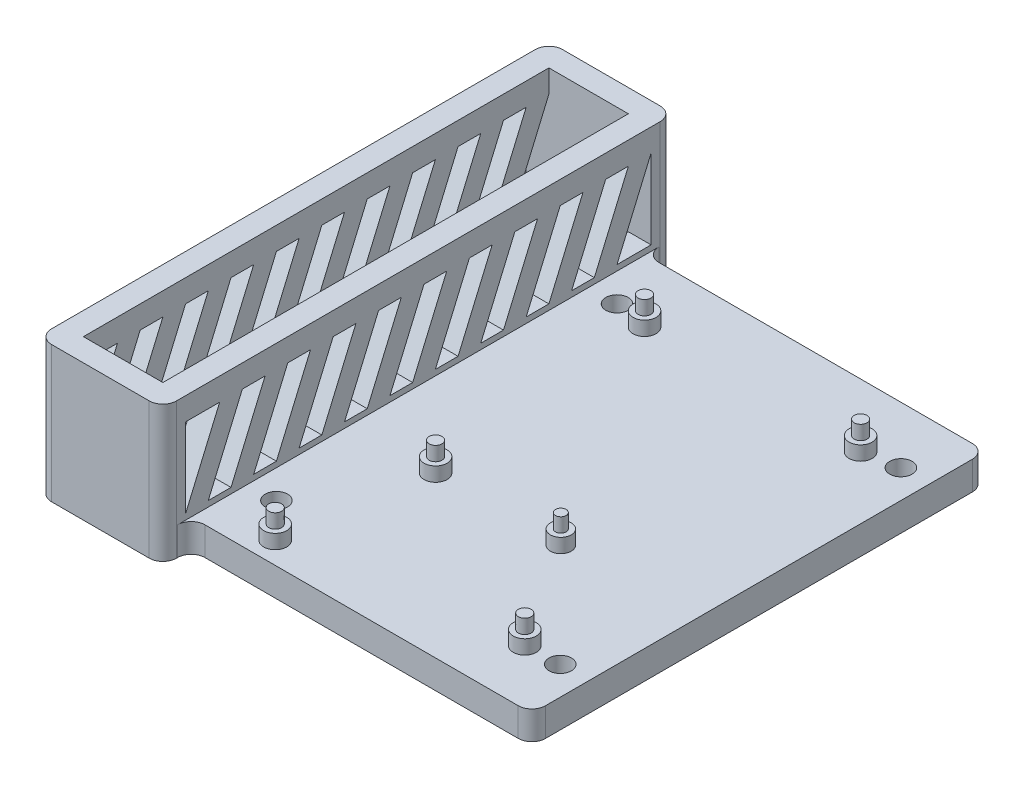
SolidWorks part; units mm, degrees
ref_plane "Front Plane" through (0, 0, 0) normal (0, 0, 1) x (1, 0, 0)
ref_plane "Top Plane" through (0, 0, 0) normal (0, 1, 0) x (1, 0, 0)
ref_plane "Right Plane" through (0, 0, 0) normal (1, 0, 0) x (0, 0, -1)
sketch "Sketch1" plane through (0, 0, 0) normal (0, 1, 0) x (1, 0, 0)
  line L1 (-38.1, -50.8) -> (38.1, -50.8)
  line L2 (-38.1, -50.8) -> (-38.1, 50.8)
  line L3 (-38.1, 50.8) -> (38.1, 50.8)
  line L4 (38.1, -50.8) -> (38.1, 50.8)
  line L5 (-38.1, -50.8) -> (38.1, 50.8) construction
  line L6 (-38.1, 50.8) -> (38.1, -50.8) construction
  circle A0 centre (-31.75, 38.1) radius 2.5
  circle A1 centre (-31.75, -38.1) radius 2.5
  circle A2 centre (31.75, 38.1) radius 2.5
  circle A3 centre (31.75, -38.1) radius 2.5
  point P0 (0, 0)
  dimension "D3" = 5
  dimension "D1" = 76.2
  dimension "D2" = 101.6
  dimension "D4" = 6.35
  dimension "D5" = 6.35
  dimension "D6" = 12.7
  dimension "D7" = 12.7
extrude "Boss-Extrude1" add sketch "Sketch1" along normal blind 6.35
sketch "Sketch2" plane through (0, 6.35, 0) normal (0, 1, 0) x (1, 0, 0)
  circle A0 centre (-24.1681, -45.9486) radius 1.5621 construction
  circle A1 centre (24.1681, -38.4556) radius 1.5621 construction
  circle A2 centre (-19.2896, -14.9479) radius 1.5621 construction
  circle A3 centre (8.7266, -14.9479) radius 1.3153 construction
  circle A4 centre (-24.1681, 36.6776) radius 1.5621 construction
  circle A5 centre (24.1681, 36.6776) radius 1.5621 construction
  circle A6 centre (-24.1681, -45.9486) radius 1.5621 construction
  circle A7 centre (24.1681, -38.4556) radius 1.5621 construction
  circle A8 centre (-19.2896, -14.9479) radius 1.5621 construction
  circle A9 centre (8.7266, -14.9479) radius 1.3153 construction
  circle A10 centre (-24.1681, 36.6776) radius 1.5621 construction
  circle A11 centre (24.1681, 36.6776) radius 1.5621 construction
  circle A12 centre (-24.1681, 36.6776) radius 2.5781
  circle A13 centre (24.1681, 36.6776) radius 2.5781
  circle A14 centre (-19.2896, -14.9479) radius 2.5781
  circle A15 centre (24.1681, -38.4556) radius 2.5781
  circle A16 centre (-24.1681, -45.9486) radius 2.5781
  circle A17 centre (-24.1681, 36.6776) radius 1.4351
  circle A18 centre (24.1681, 36.6776) radius 1.4351
  circle A19 centre (-19.2896, -14.9479) radius 1.4351
  circle A20 centre (-24.1681, -45.9486) radius 1.4351
  circle A21 centre (24.1681, -38.4556) radius 1.4351
  circle A22 centre (8.7266, -14.9479) radius 1.1883
  circle A23 centre (8.7266, -14.9479) radius 2.3313
  dimension "D1" = 1.016
  dimension "D2" = 0.127
  dimension "D3" = 0.127
  dimension "D4" = 1.016
extrude "Boss-Extrude2" add sketch "Sketch2" along normal blind 3.175 contours A17 | A12 A17 | A18 | A13 A18 | A19 | A14 A19 | A22 | A23 A22 | A20 | A16 A20 | A21 | A15 A21 region at (-26.6733, 6.35, -36.6776) region at (21.6629, 6.35, -36.6776) region at (-21.7948, 6.35, 14.9479) region at (21.6629, 6.35, 38.4556) region at (-26.6733, 6.35, 45.9486) region at (-24.1681, 6.35, -36.6776) region at (24.1681, 6.35, -36.6776) region at (-19.2896, 6.35, 14.9479) region at (-24.1681, 6.35, 45.9486) region at (24.1681, 6.35, 38.4556) region at (8.7266, 6.35, 14.9479) region at (6.4613, 6.35, 14.9479)
extrude "Boss-Extrude3" add sketch "Sketch2<4>" along normal blind 3.175 from surface contours A17 | A18 | A19 | A22 | A21 | A20 region at (-24.1681, 6.35, -36.6776) region at (24.1681, 6.35, -36.6776) region at (-19.2896, 6.35, 14.9479) region at (-24.1681, 6.35, 45.9486) region at (24.1681, 6.35, 38.4556) region at (8.7266, 6.35, 14.9479) starting at face at (-24.1681, 9.525, -34.0995)
sketch "Sketch2<4>" plane through (0, 6.35, 0) normal (0, 1, 0) x (1, 0, 0) same geometry as "Sketch2"
sketch "Sketch4" plane through (0, 0, 0) normal (0, -1, 0) x (1, 0, 0)
  line L0 (38.1, 50.8) -> (38.1, -50.8) construction
  line L5 (38.1, 57.15) -> (66.04, 57.15)
  line L6 (38.1, 57.15) -> (38.1, -57.15)
  line L7 (38.1, -57.15) -> (66.04, -57.15)
  line L8 (66.04, 57.15) -> (66.04, -57.15)
  line L9 (38.1, 57.15) -> (66.04, -57.15) construction
  line L10 (38.1, -57.15) -> (66.04, 57.15) construction
  line L11 (-38.1, 50.8) -> (38.1, 50.8) construction
  line L12 (43.18, 52.07) -> (60.96, -52.07) construction
  line L13 (43.18, 52.07) -> (60.96, 52.07)
  line L14 (43.18, 52.07) -> (43.18, -52.07)
  line L15 (43.18, -52.07) -> (60.96, -52.07)
  line L16 (60.96, 52.07) -> (60.96, -52.07)
  line L17 (60.96, 52.07) -> (43.18, -52.07) construction
  line L18 (0, -1000) -> (0, 49000) construction
  line L19 (-60.96, 52.07) -> (-43.18, -52.07) construction
  line L20 (-43.18, 52.07) -> (-60.96, -52.07) construction
  line L21 (-38.1, -57.15) -> (-66.04, 57.15) construction
  line L22 (-38.1, 57.15) -> (-66.04, -57.15) construction
  line L23 (-60.96, 52.07) -> (-60.96, -52.07)
  line L24 (-43.18, -52.07) -> (-60.96, -52.07)
  line L25 (-43.18, 52.07) -> (-43.18, -52.07)
  line L26 (-43.18, 52.07) -> (-60.96, 52.07)
  line L27 (-66.04, 57.15) -> (-66.04, -57.15)
  line L28 (-38.1, -57.15) -> (-66.04, -57.15)
  line L29 (-38.1, 57.15) -> (-38.1, -57.15)
  line L30 (-38.1, 57.15) -> (-66.04, 57.15)
  point P4 (52.07, 0)
  point P5 (52.07, 0)
  point P25 (-52.07, 0)
  dimension "D1" = 6.35
  dimension "D2" = 27.94
  dimension "D3" = 5.08
  dimension "D4" = 5.08
extrude "Boss-Extrude5" add sketch "Sketch4" against normal blind 30.48 contours L23 L24 L25 L26 | L28 L27 L30 L29
fillet "Fillet4" radius 3.048 8 edges at (38.1, 3.175, 50.8) (38.1, 3.175, -50.8) (-66.04, 15.24, -57.15) (-38.1, 15.24, -57.15) (-38.1, 3.175, -50.8) (-66.04, 15.24, 57.15) (-38.1, 15.24, 57.15) (-38.1, 3.175, 50.8)
sketch "Sketch6" plane through (-43.18, 0, 0) normal (-1, 0, 0) x (0, 0, 1)
  line L0 (54.102, 30.48) -> (-54.102, 30.48) construction
  line L1 (-52.07, 25.4) -> (52.07, 25.4)
  line L2 (-52.07, 25.4) -> (-52.07, 7.62)
  line L3 (-52.07, 7.62) -> (52.07, 7.62)
  line L4 (52.07, 25.4) -> (52.07, 7.62)
  line L5 (54.102, 0) -> (-54.102, 0) construction
  line L6 (-57.15, 0) -> (-57.15, 30.48) construction
  line L7 (57.15, 30.48) -> (57.15, 0) construction
  line L8 (-52.07, 25.4) -> (-44.45, 7.62)
  line L9 (-46.99, 25.4) -> (-39.37, 7.62)
  line L10 (-41.91, 25.4) -> (-34.29, 7.62)
  line L11 (-36.83, 25.4) -> (-29.21, 7.62)
  line L12 (-31.75, 25.4) -> (-24.13, 7.62)
  line L13 (-26.67, 25.4) -> (-19.05, 7.62)
  line L14 (-21.59, 25.4) -> (-13.97, 7.62)
  line L15 (-16.51, 25.4) -> (-8.89, 7.62)
  line L16 (-11.43, 25.4) -> (-3.81, 7.62)
  line L17 (-6.35, 25.4) -> (1.27, 7.62)
  line L18 (-1.27, 25.4) -> (6.35, 7.62)
  line L19 (3.81, 25.4) -> (11.43, 7.62)
  line L20 (8.89, 25.4) -> (16.51, 7.62)
  line L21 (13.97, 25.4) -> (21.59, 7.62)
  line L22 (19.05, 25.4) -> (26.67, 7.62)
  line L23 (24.13, 25.4) -> (31.75, 7.62)
  line L24 (29.21, 25.4) -> (36.83, 7.62)
  line L25 (34.29, 25.4) -> (41.91, 7.62)
  line L26 (39.37, 25.4) -> (46.99, 7.62)
  line L27 (44.45, 25.4) -> (52.07, 7.62)
  line M26 (52.07, 0) -> (52.07, 30.48)
  line M28 (-52.07, 30.48) -> (-52.07, 0)
  dimension "D1" = 5.08
  dimension "D2" = 7.62
  dimension "D3" = 5.08
  dimension "D4" = 5.08
  dimension "D5" = 7.62
  dimension "D7" = 5.08
  dimension "D6" = 20
extrude "Cut-Extrude1" cut sketch "Sketch6" against normal blind 7.62 and the other way blind 30.48 contours L8 L3 M28 | L10 L1 L9 L3 | L12 L1 L11 L3 | L14 L1 L13 L3 | L16 L1 L15 L3 | L18 L1 L17 L3 | L20 L1 L19 L3 | L22 L1 L21 L3 | L24 L1 L23 L3 | L26 L1 L25 L3 | L1 L27 M26 region at (-43.18, 13.5467, -49.53) region at (-43.18, 16.51, -40.64) region at (-43.18, 16.51, -30.48) region at (-43.18, 16.51, -20.32) region at (-43.18, 16.51, -10.16) region at (-43.18, 16.51, 0) region at (-43.18, 16.51, 10.16) region at (-43.18, 16.51, 20.32) region at (-43.18, 16.51, 30.48) region at (-43.18, 16.51, 40.64) region at (-43.18, 19.4733, 49.53)
extrude "Boss-Extrude6" add sketch "Sketch4<6>" against normal blind 3.81 contours L25 L26 L23 L24 region at (-52.07, 0, 0)
sketch "Sketch4<6>" plane through (0, 0, 0) normal (0, -1, 0) x (1, 0, 0) same geometry as "Sketch4"
